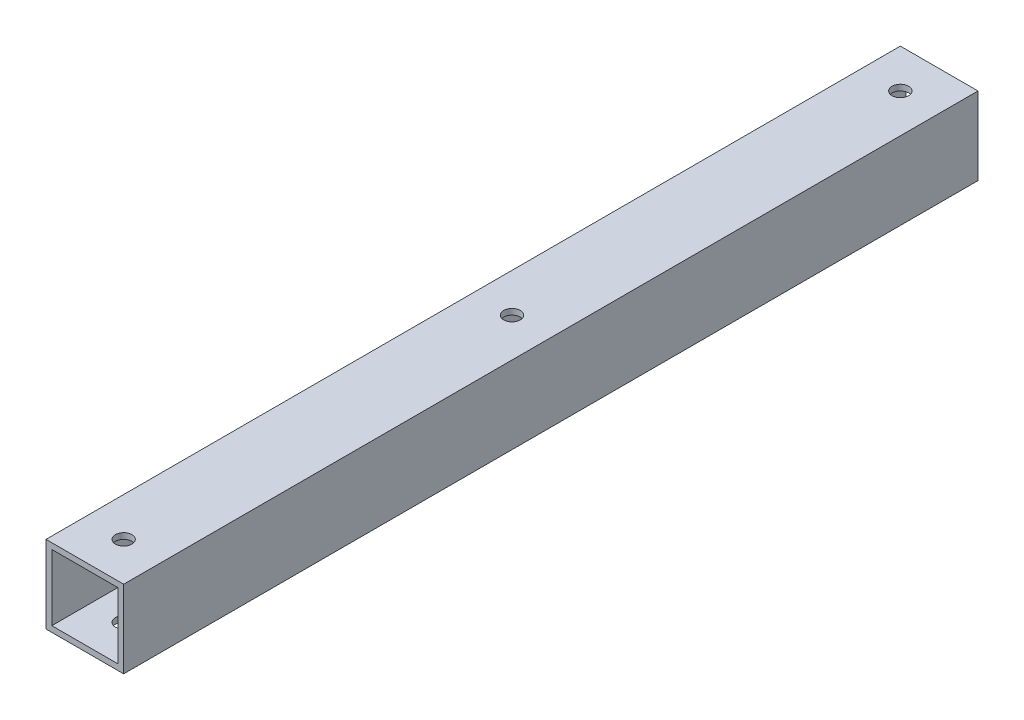
SolidWorks part; units mm, degrees
ref_plane "Front Plane" through (0, 0, 0) normal (0, 0, 1) x (1, 0, 0)
ref_plane "Top Plane" through (0, 0, 0) normal (0, 1, 0) x (1, 0, 0)
ref_plane "Right Plane" through (0, 0, 0) normal (1, 0, 0) x (0, 0, -1)
sketch "Sketch1" plane through (0, 0, 0) normal (0, 0, 1) x (1, 0, 0)
  line L0 (-8.5, -8.5) -> (8.5, -8.5)
  line L1 (-10, -10) -> (10, -10)
  line L2 (-10, -10) -> (-10, 10)
  line L3 (-10, 10) -> (10, 10)
  line L4 (10, -10) -> (10, 10)
  line L5 (-10, -10) -> (10, 10) construction
  line L6 (-10, 10) -> (10, -10) construction
  line L7 (8.5, -8.5) -> (8.5, 8.5)
  line L8 (-8.5, 8.5) -> (8.5, 8.5)
  line L9 (-8.5, -8.5) -> (-8.5, 8.5)
  point P0 (0, 0)
  dimension "D1" = 20
  dimension "D3" = 20
  dimension "D2" = 1.5
extrude "Boss-Extrude1" add sketch "Sketch1" against normal blind 220
sketch "Sketch2" plane through (0, 10, 0) normal (0, 1, 0) x (1, 0, 0)
  line L0 (10, 0) -> (-10, 0) construction
  circle A0 centre (0, 10) radius 2.125
  circle A1 centre (0, 60) radius 2.125 construction
  circle A2 centre (0, 110) radius 2.125
  circle A3 centre (0, 160) radius 2.125 construction
  circle A4 centre (0, 210) radius 2.125
  dimension "D1" = 4.25
  dimension "D2" = 10
  dimension "D4" = 50
  dimension "D3" = 5
extrude "Cut-Extrude1" cut sketch "Sketch2" against normal through all
